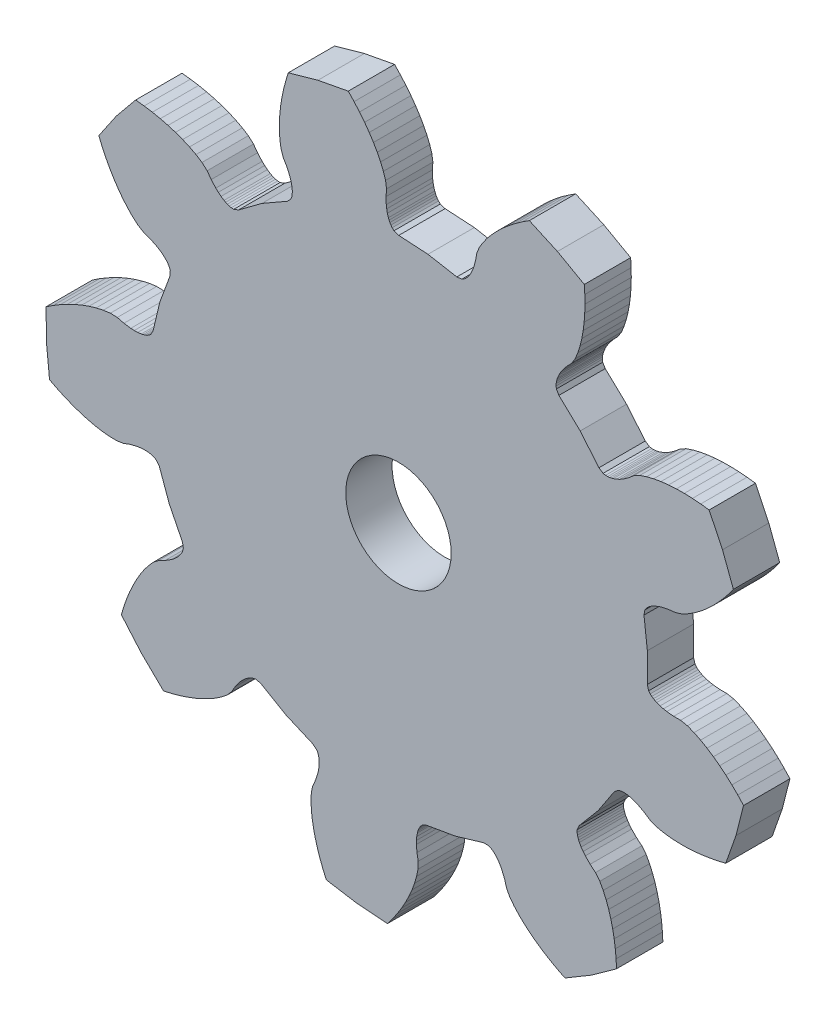
SolidWorks part; units mm, degrees
ref_plane "Front Plane" through (0, 0, 0) normal (0, 0, 1) x (1, 0, 0)
ref_plane "Top Plane" through (0, 0, 0) normal (0, 1, 0) x (1, 0, 0)
ref_plane "Right Plane" through (0, 0, 0) normal (1, 0, 0) x (0, 0, -1)
sketch "Sketch2" plane through (0, 0, 0) normal (0, 0, 1) x (1, 0, 0)
  line B0 (-34.2742, -4.342) -> (-34.5965, -3.9)
  line B1 (-34.5965, -3.9) -> (-34.8297, -3.7619)
  line B2 (-34.8297, -3.7619) -> (-35.0471, -3.6778)
  line B3 (-35.0471, -3.6778) -> (-35.2561, -3.6237)
  line B4 (-35.2561, -3.6237) -> (-35.4598, -3.5899)
  line B5 (-35.4598, -3.5899) -> (-35.6592, -3.5714)
  line B6 (-35.6592, -3.5714) -> (-36.0489, -3.5686)
  line B7 (-36.0489, -3.5686) -> (-36.4296, -3.6016)
  line B8 (-36.4296, -3.6016) -> (-36.8032, -3.6628)
  line B9 (-36.8032, -3.6628) -> (-37.534, -3.8523)
  line B10 (-37.534, -3.8523) -> (-38.2467, -4.1154)
  line B11 (-38.2467, -4.1154) -> (-38.9968, -4.2267)
  line B12 (-38.9968, -4.2267) -> (-39.7783, -4.2071)
  line B13 (-39.7783, -4.2071) -> (-40.5741, -4.1215)
  line B14 (-40.5741, -4.1215) -> (-41.3803, -3.9793)
  line B15 (-41.3803, -3.9793) -> (-42.1946, -3.7852)
  line B16 (-42.1946, -3.7852) -> (-43.0148, -3.5424)
  line B17 (-43.0148, -3.5424) -> (-43.839, -3.2531)
  line B18 (-43.839, -3.2531) -> (-44.6661, -2.9186)
  line B19 (-44.6661, -2.9186) -> (-45.4939, -2.5401)
  line B20 (-45.4939, -2.5401) -> (-46.3214, -2.1185)
  line B21 (-46.3214, -2.1185) -> (-46.6574, 1.2447)
  line B22 (-46.6574, 1.2447) -> (-46.6983, 4.6242)
  line B23 (-46.6983, 4.6242) -> (-45.9231, 5.1355)
  line B24 (-45.9231, 5.1355) -> (-45.1426, 5.6039)
  line B25 (-45.1426, 5.6039) -> (-44.358, 6.0286)
  line B26 (-44.358, 6.0286) -> (-43.5711, 6.4081)
  line B27 (-43.5711, 6.4081) -> (-42.7832, 6.7405)
  line B28 (-42.7832, 6.7405) -> (-41.9955, 7.0243)
  line B29 (-41.9955, 7.0243) -> (-41.2101, 7.2554)
  line B30 (-41.2101, 7.2554) -> (-40.4291, 7.4291)
  line B31 (-40.4291, 7.4291) -> (-39.6544, 7.5358)
  line B32 (-39.6544, 7.5358) -> (-38.8965, 7.5089)
  line B33 (-38.8965, 7.5089) -> (-38.1591, 7.3268)
  line B34 (-38.1591, 7.3268) -> (-37.4118, 7.2198)
  line B35 (-37.4118, 7.2198) -> (-37.0336, 7.2008)
  line B36 (-37.0336, 7.2008) -> (-36.6516, 7.2104)
  line B37 (-36.6516, 7.2104) -> (-36.2645, 7.2564)
  line B38 (-36.2645, 7.2564) -> (-36.0684, 7.2973)
  line B39 (-36.0684, 7.2973) -> (-35.87, 7.3534)
  line B40 (-35.87, 7.3534) -> (-35.6681, 7.4307)
  line B41 (-35.6681, 7.4307) -> (-35.4614, 7.5384)
  line B42 (-35.4614, 7.5384) -> (-35.2452, 7.7017)
  line B43 (-35.2452, 7.7017) -> (-34.9742, 8.1769)
  line B44 (-34.9742, 8.1769) -> (-34.2279, 11.3014)
  line B45 (-34.2279, 11.3014) -> (-33.1205, 14.3166)
  line B46 (-33.1205, 14.3166) -> (-33.0832, 14.8624)
  line B47 (-33.0832, 14.8624) -> (-33.1728, 15.118)
  line B48 (-33.1728, 15.118) -> (-33.2856, 15.3222)
  line B49 (-33.2856, 15.3222) -> (-33.4111, 15.498)
  line B50 (-33.4111, 15.498) -> (-33.5452, 15.6547)
  line B51 (-33.5452, 15.6547) -> (-33.6859, 15.7972)
  line B52 (-33.6859, 15.7972) -> (-33.9828, 16.0499)
  line B53 (-33.9828, 16.0499) -> (-34.2958, 16.2691)
  line B54 (-34.2958, 16.2691) -> (-34.6211, 16.4626)
  line B55 (-34.6211, 16.4626) -> (-35.3029, 16.7873)
  line B56 (-35.3029, 16.7873) -> (-36.0179, 17.0435)
  line B57 (-36.0179, 17.0435) -> (-36.664, 17.4405)
  line B58 (-36.664, 17.4405) -> (-37.2503, 17.9579)
  line B59 (-37.2503, 17.9579) -> (-37.8048, 18.535)
  line B60 (-37.8048, 18.535) -> (-38.3308, 19.1622)
  line B61 (-38.3308, 19.1622) -> (-38.8299, 19.8342)
  line B62 (-38.8299, 19.8342) -> (-39.3021, 20.5475)
  line B63 (-39.3021, 20.5475) -> (-39.7476, 21.2991)
  line B64 (-39.7476, 21.2991) -> (-40.1662, 22.0867)
  line B65 (-40.1662, 22.0867) -> (-40.5571, 22.9089)
  line B66 (-40.5571, 22.9089) -> (-40.9198, 23.7636)
  line B67 (-40.9198, 23.7636) -> (-39.0153, 26.5558)
  line B68 (-39.0153, 26.5558) -> (-36.8744, 29.171)
  line B69 (-36.8744, 29.171) -> (-35.9521, 29.0646)
  line B70 (-35.9521, 29.0646) -> (-35.0529, 28.9216)
  line B71 (-35.0529, 28.9216) -> (-34.1792, 28.7425)
  line B72 (-34.1792, 28.7425) -> (-33.3323, 28.5274)
  line B73 (-33.3323, 28.5274) -> (-32.515, 28.2757)
  line B74 (-32.515, 28.2757) -> (-31.7293, 27.9869)
  line B75 (-31.7293, 27.9869) -> (-30.979, 27.6592)
  line B76 (-30.979, 27.6592) -> (-30.2688, 27.2902)
  line B77 (-30.2688, 27.2902) -> (-29.6069, 26.8739)
  line B78 (-29.6069, 26.8739) -> (-29.0438, 26.3661)
  line B79 (-29.0438, 26.3661) -> (-28.596, 25.7524)
  line B80 (-28.596, 25.7524) -> (-28.0921, 25.1903)
  line B81 (-28.0921, 25.1903) -> (-27.8147, 24.9325)
  line B82 (-27.8147, 24.9325) -> (-27.5157, 24.6945)
  line B83 (-27.5157, 24.6945) -> (-27.1898, 24.4809)
  line B84 (-27.1898, 24.4809) -> (-27.0133, 24.3859)
  line B85 (-27.0133, 24.3859) -> (-26.8251, 24.3016)
  line B86 (-26.8251, 24.3016) -> (-26.6209, 24.231)
  line B87 (-26.6209, 24.231) -> (-26.3933, 24.1804)
  line B88 (-26.3933, 24.1804) -> (-26.1228, 24.1667)
  line B89 (-26.1228, 24.1667) -> (-25.6097, 24.3565)
  line B90 (-25.6097, 24.3565) -> (-23.0298, 26.2703)
  line B91 (-23.0298, 26.2703) -> (-20.2432, 27.8683)
  line B92 (-20.2432, 27.8683) -> (-19.8637, 28.2625)
  line B93 (-19.8637, 28.2625) -> (-19.7682, 28.516)
  line B94 (-19.7682, 28.516) -> (-19.7233, 28.7448)
  line B95 (-19.7233, 28.7448) -> (-19.7062, 28.96)
  line B96 (-19.7062, 28.96) -> (-19.7083, 29.1665)
  line B97 (-19.7083, 29.1665) -> (-19.7245, 29.3661)
  line B98 (-19.7245, 29.3661) -> (-19.7898, 29.7504)
  line B99 (-19.7898, 29.7504) -> (-19.8884, 30.1195)
  line B100 (-19.8884, 30.1195) -> (-20.0133, 30.4768)
  line B101 (-20.0133, 30.4768) -> (-20.3268, 31.1637)
  line B102 (-20.3268, 31.1637) -> (-20.7098, 31.8197)
  line B103 (-20.7098, 31.8197) -> (-20.9496, 32.5391)
  line B104 (-20.9496, 32.5391) -> (-21.0662, 33.3122)
  line B105 (-21.0662, 33.3122) -> (-21.12, 34.1108)
  line B106 (-21.12, 34.1108) -> (-21.1198, 34.9295)
  line B107 (-21.1198, 34.9295) -> (-21.0702, 35.7649)
  line B108 (-21.0702, 35.7649) -> (-20.9735, 36.6148)
  line B109 (-20.9735, 36.6148) -> (-20.8317, 37.4768)
  line B110 (-20.8317, 37.4768) -> (-20.6458, 38.3493)
  line B111 (-20.6458, 38.3493) -> (-20.4169, 39.2304)
  line B112 (-20.4169, 39.2304) -> (-20.1452, 40.1184)
  line B113 (-20.1452, 40.1184) -> (-16.8917, 41.0333)
  line B114 (-16.8917, 41.0333) -> (-13.5706, 41.6605)
  line B115 (-13.5706, 41.6605) -> (-12.9323, 40.9858)
  line B116 (-12.9323, 40.9858) -> (-12.3354, 40.2985)
  line B117 (-12.3354, 40.2985) -> (-11.7812, 39.5998)
  line B118 (-11.7812, 39.5998) -> (-11.2709, 38.8906)
  line B119 (-11.2709, 38.8906) -> (-10.8063, 38.1723)
  line B120 (-10.8063, 38.1723) -> (-10.3903, 37.4461)
  line B121 (-10.3903, 37.4461) -> (-10.0263, 36.7128)
  line B122 (-10.0263, 36.7128) -> (-9.7195, 35.9737)
  line B123 (-9.7195, 35.9737) -> (-9.48, 35.2292)
  line B124 (-9.48, 35.2292) -> (-9.3748, 34.4781)
  line B125 (-9.3748, 34.4781) -> (-9.4261, 33.7204)
  line B126 (-9.4261, 33.7204) -> (-9.4017, 32.9658)
  line B127 (-9.4017, 32.9658) -> (-9.3547, 32.5901)
  line B128 (-9.3547, 32.5901) -> (-9.279, 32.2155)
  line B129 (-9.279, 32.2155) -> (-9.1665, 31.8423)
  line B130 (-9.1665, 31.8423) -> (-9.0923, 31.6564)
  line B131 (-9.0923, 31.6564) -> (-9.0024, 31.4705)
  line B132 (-9.0024, 31.4705) -> (-8.8914, 31.2853)
  line B133 (-8.8914, 31.2853) -> (-8.7494, 31.1004)
  line B134 (-8.7494, 31.1004) -> (-8.5511, 30.9158)
  line B135 (-8.5511, 30.9158) -> (-8.036, 30.7313)
  line B136 (-8.036, 30.7313) -> (-4.8295, 30.5391)
  line B137 (-4.8295, 30.5391) -> (-1.6677, 29.9719)
  line B138 (-1.6677, 29.9719) -> (-1.1236, 30.0301)
  line B139 (-1.1236, 30.0301) -> (-0.8874, 30.1629)
  line B140 (-0.8874, 30.1629) -> (-0.706, 30.3092)
  line B141 (-0.706, 30.3092) -> (-0.5546, 30.4634)
  line B142 (-0.5546, 30.4634) -> (-0.4236, 30.6226)
  line B143 (-0.4236, 30.6226) -> (-0.3078, 30.786)
  line B144 (-0.3078, 30.786) -> (-0.1107, 31.1223)
  line B145 (-0.1107, 31.1223) -> (0.0511, 31.4685)
  line B146 (0.0511, 31.4685) -> (0.1853, 31.8225)
  line B147 (0.1853, 31.8225) -> (0.3864, 32.5502)
  line B148 (0.3864, 32.5502) -> (0.5147, 33.299)
  line B149 (0.5147, 33.299) -> (0.7936, 34.0041)
  line B150 (0.7936, 34.0041) -> (1.2013, 34.6714)
  line B151 (1.2013, 34.6714) -> (1.6732, 35.3176)
  line B152 (1.6732, 35.3176) -> (2.1995, 35.9447)
  line B153 (2.1995, 35.9447) -> (2.7748, 36.5528)
  line B154 (2.7748, 36.5528) -> (3.3951, 37.1418)
  line B155 (3.3951, 37.1418) -> (4.0577, 37.711)
  line B156 (4.0577, 37.711) -> (4.7611, 38.2599)
  line B157 (4.7611, 38.2599) -> (5.5027, 38.7877)
  line B158 (5.5027, 38.7877) -> (6.2815, 39.2932)
  line B159 (6.2815, 39.2932) -> (9.362, 37.9028)
  line B160 (9.362, 37.9028) -> (12.3094, 36.2485)
  line B161 (12.3094, 36.2485) -> (12.3646, 35.3214)
  line B162 (12.3646, 35.3214) -> (12.38, 34.4113)
  line B163 (12.38, 34.4113) -> (12.3554, 33.5195)
  line B164 (12.3554, 33.5195) -> (12.2906, 32.6483)
  line B165 (12.2906, 32.6483) -> (12.1847, 31.7997)
  line B166 (12.1847, 31.7997) -> (12.0364, 30.9757)
  line B167 (12.0364, 30.9757) -> (11.8441, 30.1799)
  line B168 (11.8441, 30.1799) -> (11.6038, 29.4166)
  line B169 (11.6038, 29.4166) -> (11.3089, 28.6925)
  line B170 (11.3089, 28.6925) -> (10.9066, 28.0496)
  line B171 (10.9066, 28.0496) -> (10.3803, 27.502)
  line B172 (10.3803, 27.502) -> (9.914, 26.9084)
  line B173 (9.914, 26.9084) -> (9.7085, 26.5904)
  line B174 (9.7085, 26.5904) -> (9.5259, 26.2546)
  line B175 (9.5259, 26.2546) -> (9.3722, 25.8965)
  line B176 (9.3722, 25.8965) -> (9.3094, 25.7062)
  line B177 (9.3094, 25.7062) -> (9.2589, 25.5061)
  line B178 (9.2589, 25.5061) -> (9.2246, 25.293)
  line B179 (9.2246, 25.293) -> (9.2147, 25.06)
  line B180 (9.2147, 25.06) -> (9.248, 24.7911)
  line B181 (9.248, 24.7911) -> (9.5238, 24.3186)
  line B182 (9.5238, 24.3186) -> (11.8568, 22.1103)
  line B183 (11.8568, 22.1103) -> (13.9142, 19.6435)
  line B184 (13.9142, 19.6435) -> (14.3684, 19.3384)
  line B185 (14.3684, 19.3384) -> (14.6346, 19.2881)
  line B186 (14.6346, 19.2881) -> (14.8677, 19.2838)
  line B187 (14.8677, 19.2838) -> (15.0826, 19.3044)
  line B188 (15.0826, 19.3044) -> (15.2856, 19.3422)
  line B189 (15.2856, 19.3422) -> (15.4794, 19.393)
  line B190 (15.4794, 19.393) -> (15.8464, 19.5239)
  line B191 (15.8464, 19.5239) -> (16.1928, 19.6851)
  line B192 (16.1928, 19.6851) -> (16.5233, 19.8703)
  line B193 (16.5233, 19.8703) -> (17.1451, 20.2983)
  line B194 (17.1451, 20.2983) -> (17.7245, 20.7893)
  line B195 (17.7245, 20.7893) -> (18.3915, 21.1502)
  line B196 (18.3915, 21.1502) -> (19.1326, 21.3994)
  line B197 (19.1326, 21.3994) -> (19.9096, 21.5909)
  line B198 (19.9096, 21.5909) -> (20.7158, 21.7331)
  line B199 (20.7158, 21.7331) -> (21.5474, 21.8292)
  line B200 (21.5474, 21.8292) -> (22.4011, 21.8817)
  line B201 (22.4011, 21.8817) -> (23.2749, 21.8916)
  line B202 (23.2749, 21.8916) -> (24.1662, 21.8601)
  line B203 (24.1662, 21.8601) -> (25.0737, 21.7878)
  line B204 (25.0737, 21.7878) -> (25.9955, 21.6745)
  line B205 (25.9955, 21.6745) -> (27.4613, 18.629)
  line B206 (27.4613, 18.629) -> (28.6556, 15.4672)
  line B207 (28.6556, 15.4672) -> (28.1021, 14.7217)
  line B208 (28.1021, 14.7217) -> (27.5289, 14.0146)
  line B209 (27.5289, 14.0146) -> (26.9368, 13.3473)
  line B210 (26.9368, 13.3473) -> (26.3272, 12.7215)
  line B211 (26.3272, 12.7215) -> (25.7003, 12.1396)
  line B212 (25.7003, 12.1396) -> (25.0574, 11.6036)
  line B213 (25.0574, 11.6036) -> (24.3986, 11.1177)
  line B214 (24.3986, 11.1177) -> (23.7239, 10.6872)
  line B215 (23.7239, 10.6872) -> (23.0323, 10.3222)
  line B216 (23.0323, 10.3222) -> (22.3109, 10.0883)
  line B217 (22.3109, 10.0883) -> (21.5558, 10.0072)
  line B218 (21.5558, 10.0072) -> (20.8169, 9.852)
  line B219 (20.8169, 9.852) -> (20.4552, 9.7405)
  line B220 (20.4552, 9.7405) -> (20.0994, 9.6008)
  line B221 (20.0994, 9.6008) -> (19.7514, 9.4253)
  line B222 (19.7514, 9.4253) -> (19.5812, 9.3199)
  line B223 (19.5812, 9.3199) -> (19.4138, 9.199)
  line B224 (19.4138, 9.199) -> (19.2505, 9.0575)
  line B225 (19.2505, 9.0575) -> (19.093, 8.8858)
  line B226 (19.093, 8.8858) -> (18.9459, 8.6582)
  line B227 (18.9459, 8.6582) -> (18.8535, 8.119)
  line B228 (18.8535, 8.119) -> (19.221, 4.9277)
  line B229 (19.221, 4.9277) -> (19.2116, 1.7157)
  line B230 (19.2116, 1.7157) -> (19.3633, 1.1901)
  line B231 (19.3633, 1.1901) -> (19.5352, 0.9803)
  line B232 (19.5352, 0.9803) -> (19.7107, 0.8272)
  line B233 (19.7107, 0.8272) -> (19.8888, 0.7047)
  line B234 (19.8888, 0.7047) -> (20.0684, 0.6034)
  line B235 (20.0684, 0.6034) -> (20.2495, 0.5175)
  line B236 (20.2495, 0.5175) -> (20.615, 0.3819)
  line B237 (20.615, 0.3819) -> (20.9838, 0.2826)
  line B238 (20.9838, 0.2826) -> (21.3559, 0.2122)
  line B239 (21.3559, 0.2122) -> (22.1075, 0.1404)
  line B240 (22.1075, 0.1404) -> (22.8669, 0.1442)
  line B241 (22.8669, 0.1442) -> (23.6099, -0.008)
  line B242 (23.6099, -0.008) -> (24.3379, -0.2937)
  line B243 (24.3379, -0.2937) -> (25.0562, -0.6463)
  line B244 (25.0562, -0.6463) -> (25.7651, -1.0557)
  line B245 (25.7651, -1.0557) -> (26.4638, -1.5165)
  line B246 (26.4638, -1.5165) -> (27.1517, -2.0253)
  line B247 (27.1517, -2.0253) -> (27.8273, -2.579)
  line B248 (27.8273, -2.579) -> (28.49, -3.1761)
  line B249 (28.49, -3.1761) -> (29.1385, -3.8149)
  line B250 (29.1385, -3.8149) -> (29.7717, -4.4944)
  line B251 (29.7717, -4.4944) -> (28.9373, -7.7695)
  line B252 (28.9373, -7.7695) -> (27.8199, -10.9592)
  line B253 (27.8199, -10.9592) -> (26.9165, -11.1746)
  line B254 (26.9165, -11.1746) -> (26.0229, -11.3478)
  line B255 (26.0229, -11.3478) -> (25.1405, -11.4784)
  line B256 (25.1405, -11.4784) -> (24.2711, -11.5657)
  line B257 (24.2711, -11.5657) -> (23.4169, -11.6089)
  line B258 (23.4169, -11.6089) -> (22.5799, -11.6061)
  line B259 (22.5799, -11.6061) -> (21.7628, -11.5548)
  line B260 (21.7628, -11.5548) -> (20.9693, -11.4507)
  line B261 (20.9693, -11.4507) -> (20.205, -11.2861)
  line B262 (20.205, -11.2861) -> (19.502, -11.0016)
  line B263 (19.502, -11.0016) -> (18.8713, -10.5782)
  line B264 (18.8713, -10.5782) -> (18.2055, -10.2221)
  line B265 (18.2055, -10.2221) -> (17.8568, -10.075)
  line B266 (17.8568, -10.075) -> (17.4946, -9.9534)
  line B267 (17.4946, -9.9534) -> (17.1151, -9.8642)
  line B268 (17.1151, -9.8642) -> (16.9167, -9.8352)
  line B269 (16.9167, -9.8352) -> (16.711, -9.8205)
  line B270 (16.711, -9.8205) -> (16.4951, -9.8238)
  line B271 (16.4951, -9.8238) -> (16.264, -9.8543)
  line B272 (16.264, -9.8543) -> (16.0049, -9.9338)
  line B273 (16.0049, -9.9338) -> (15.5876, -10.2876)
  line B274 (15.5876, -10.2876) -> (13.8179, -12.9683)
  line B275 (13.8179, -12.9683) -> (11.7458, -15.423)
  line B276 (11.7458, -15.423) -> (11.5243, -15.9234)
  line B277 (11.5243, -15.9234) -> (11.521, -16.1941)
  line B278 (11.521, -16.1941) -> (11.5571, -16.4245)
  line B279 (11.5571, -16.4245) -> (11.6147, -16.6328)
  line B280 (11.6147, -16.6328) -> (11.6871, -16.8258)
  line B281 (11.6871, -16.8258) -> (11.771, -17.008)
  line B282 (11.771, -17.008) -> (11.9635, -17.3468)
  line B283 (11.9635, -17.3468) -> (12.1824, -17.66)
  line B284 (12.1824, -17.66) -> (12.4222, -17.9531)
  line B285 (12.4222, -17.9531) -> (12.9515, -18.4911)
  line B286 (12.9515, -18.4911) -> (13.5357, -18.9767)
  line B287 (13.5357, -18.9767) -> (14.0072, -19.5706)
  line B288 (14.0072, -19.5706) -> (14.3811, -20.2574)
  line B289 (14.3811, -20.2574) -> (14.7049, -20.9891)
  line B290 (14.7049, -20.9891) -> (14.9848, -21.7585)
  line B291 (14.9848, -21.7585) -> (15.2238, -22.5606)
  line B292 (15.2238, -22.5606) -> (15.4237, -23.3925)
  line B293 (15.4237, -23.3925) -> (15.5853, -24.251)
  line B294 (15.5853, -24.251) -> (15.709, -25.1344)
  line B295 (15.709, -25.1344) -> (15.7951, -26.0407)
  line B296 (15.7951, -26.0407) -> (15.8436, -26.9681)
  line B297 (15.8436, -26.9681) -> (13.0991, -28.9406)
  line B298 (13.0991, -28.9406) -> (10.1929, -30.6658)
  line B299 (10.1929, -30.6658) -> (9.3625, -30.25)
  line B300 (9.3625, -30.25) -> (8.5665, -29.8083)
  line B301 (8.5665, -29.8083) -> (7.8065, -29.3412)
  line B302 (7.8065, -29.3412) -> (7.0847, -28.8494)
  line B303 (7.0847, -28.8494) -> (6.4024, -28.3333)
  line B304 (6.4024, -28.3333) -> (5.7631, -27.793)
  line B305 (5.7631, -27.793) -> (5.1703, -27.2287)
  line B306 (5.1703, -27.2287) -> (4.629, -26.6389)
  line B307 (4.629, -26.6389) -> (4.1494, -26.0214)
  line B308 (4.1494, -26.0214) -> (3.7938, -25.3516)
  line B309 (3.7938, -25.3516) -> (3.5828, -24.6219)
  line B310 (3.5828, -24.6219) -> (3.3018, -23.9213)
  line B311 (3.3018, -23.9213) -> (3.1291, -23.5843)
  line B312 (3.1291, -23.5843) -> (2.9297, -23.2581)
  line B313 (2.9297, -23.2581) -> (2.6963, -22.946)
  line B314 (2.6963, -22.946) -> (2.5632, -22.7966)
  line B315 (2.5632, -22.7966) -> (2.4151, -22.6528)
  line B316 (2.4151, -22.6528) -> (2.2475, -22.5167)
  line B317 (2.2475, -22.5167) -> (2.0509, -22.3915)
  line B318 (2.0509, -22.3915) -> (1.8012, -22.2858)
  line B319 (1.8012, -22.2858) -> (1.2541, -22.2886)
  line B320 (1.2541, -22.2886) -> (-1.8246, -23.2048)
  line B321 (-1.8246, -23.2048) -> (-4.9897, -23.7532)
  line B322 (-4.9897, -23.7532) -> (-5.481, -23.994)
  line B323 (-5.481, -23.994) -> (-5.6578, -24.1995)
  line B324 (-5.6578, -24.1995) -> (-5.7782, -24.3991)
  line B325 (-5.7782, -24.3991) -> (-5.8678, -24.5954)
  line B326 (-5.8678, -24.5954) -> (-5.9364, -24.79)
  line B327 (-5.9364, -24.79) -> (-5.9895, -24.9833)
  line B328 (-5.9895, -24.9833) -> (-6.0596, -25.3666)
  line B329 (-6.0596, -25.3666) -> (-6.0931, -25.7473)
  line B330 (-6.0931, -25.7473) -> (-6.0979, -26.126)
  line B331 (-6.0979, -26.126) -> (-6.0383, -26.8784)
  line B332 (-6.0383, -26.8784) -> (-5.9029, -27.6259)
  line B333 (-5.9029, -27.6259) -> (-5.9234, -28.3838)
  line B334 (-5.9234, -28.3838) -> (-6.0784, -29.1504)
  line B335 (-6.0784, -29.1504) -> (-6.3009, -29.919)
  line B336 (-6.3009, -29.919) -> (-6.5811, -30.6884)
  line B337 (-6.5811, -30.6884) -> (-6.9135, -31.4565)
  line B338 (-6.9135, -31.4565) -> (-7.295, -32.222)
  line B339 (-7.295, -32.222) -> (-7.723, -32.9838)
  line B340 (-7.723, -32.9838) -> (-8.1962, -33.7399)
  line B341 (-8.1962, -33.7399) -> (-8.7126, -34.4895)
  line B342 (-8.7126, -34.4895) -> (-9.2717, -35.2312)
  line B343 (-9.2717, -35.2312) -> (-12.642, -34.9782)
  line B344 (-12.642, -34.9782) -> (-15.9773, -34.4316)
  line B345 (-15.9773, -34.4316) -> (-16.3461, -33.5794)
  line B346 (-16.3461, -33.5794) -> (-16.672, -32.7293)
  line B347 (-16.672, -32.7293) -> (-16.9539, -31.883)
  line B348 (-16.9539, -31.883) -> (-17.1909, -31.0422)
  line B349 (-17.1909, -31.0422) -> (-17.3816, -30.2083)
  line B350 (-17.3816, -30.2083) -> (-17.5241, -29.3836)
  line B351 (-17.5241, -29.3836) -> (-17.6156, -28.57)
  line B352 (-17.6156, -28.57) -> (-17.6509, -27.7704)
  line B353 (-17.6509, -27.7704) -> (-17.6214, -26.9891)
  line B354 (-17.6214, -26.9891) -> (-17.4634, -26.2475)
  line B355 (-17.4634, -26.2475) -> (-17.1558, -25.5528)
  line B356 (-17.1558, -25.5528) -> (-16.9209, -24.8355)
  line B357 (-16.9209, -24.8355) -> (-16.8366, -24.4662)
  line B358 (-16.8366, -24.4662) -> (-16.7797, -24.0885)
  line B359 (-16.7797, -24.0885) -> (-16.7578, -23.6993)
  line B360 (-16.7578, -23.6993) -> (-16.7639, -23.4989)
  line B361 (-16.7639, -23.4989) -> (-16.7847, -23.2937)
  line B362 (-16.7847, -23.2937) -> (-16.8256, -23.0816)
  line B363 (-16.8256, -23.0816) -> (-16.8957, -22.8593)
  line B364 (-16.8957, -22.8593) -> (-17.0192, -22.618)
  line B365 (-17.0192, -22.618) -> (-17.4401, -22.2685)
  line B366 (-17.4401, -22.2685) -> (-20.3875, -20.9912)
  line B367 (-20.3875, -20.9912) -> (-23.1645, -19.3768)
  line B368 (-23.1645, -19.3768) -> (-23.6956, -19.2454)
  line B369 (-23.6956, -19.2454) -> (-23.963, -19.2894)
  line B370 (-23.963, -19.2894) -> (-24.1835, -19.3648)
  line B371 (-24.1835, -19.3648) -> (-24.3786, -19.4578)
  line B372 (-24.3786, -19.4578) -> (-24.5561, -19.5627)
  line B373 (-24.5561, -19.5627) -> (-24.721, -19.6767)
  line B374 (-24.721, -19.6767) -> (-25.0212, -19.9254)
  line B375 (-25.0212, -19.9254) -> (-25.2917, -20.1951)
  line B376 (-25.2917, -20.1951) -> (-25.5386, -20.4822)
  line B377 (-25.5386, -20.4822) -> (-25.9765, -21.0971)
  line B378 (-25.9765, -21.0971) -> (-26.3532, -21.7567)
  line B379 (-26.3532, -21.7567) -> (-26.8563, -22.3242)
  line B380 (-26.8563, -22.3242) -> (-27.4677, -22.8116)
  line B381 (-27.4677, -22.8116) -> (-28.1324, -23.2576)
  line B382 (-28.1324, -23.2576) -> (-28.8414, -23.6668)
  line B383 (-28.8414, -23.6668) -> (-29.5899, -24.0415)
  line B384 (-29.5899, -24.0415) -> (-30.3742, -24.3828)
  line B385 (-30.3742, -24.3828) -> (-31.1916, -24.6909)
  line B386 (-31.1916, -24.6909) -> (-32.0402, -24.9663)
  line B387 (-32.0402, -24.9663) -> (-32.9175, -25.2083)
  line B388 (-32.9175, -25.2083) -> (-33.8226, -25.4171)
  line B389 (-33.8226, -25.4171) -> (-36.2416, -23.057)
  line B390 (-36.2416, -23.057) -> (-38.4454, -20.4944)
  line B391 (-38.4454, -20.4944) -> (-38.1802, -19.6046)
  line B392 (-38.1802, -19.6046) -> (-37.8832, -18.7438)
  line B393 (-37.8832, -18.7438) -> (-37.5553, -17.9145)
  line B394 (-37.5553, -17.9145) -> (-37.1964, -17.1179)
  line B395 (-37.1964, -17.1179) -> (-36.8065, -16.3564)
  line B396 (-36.8065, -16.3564) -> (-36.3854, -15.633)
  line B397 (-36.3854, -15.633) -> (-35.9325, -14.9511)
  line B398 (-35.9325, -14.9511) -> (-35.4459, -14.3158)
  line B399 (-35.4459, -14.3158) -> (-34.9208, -13.7364)
  line B400 (-34.9208, -13.7364) -> (-34.3232, -13.2698)
  line B401 (-34.3232, -13.2698) -> (-33.6412, -12.9353)
  line B402 (-33.6412, -12.9353) -> (-32.9998, -12.5368)
  line B403 (-32.9998, -12.5368) -> (-32.6981, -12.3082)
  line B404 (-32.6981, -12.3082) -> (-32.4116, -12.0555)
  line B405 (-32.4116, -12.0555) -> (-32.1446, -11.7712)
  line B406 (-32.1446, -11.7712) -> (-32.0207, -11.614)
  line B407 (-32.0207, -11.614) -> (-31.9046, -11.4433)
  line B408 (-31.9046, -11.4433) -> (-31.7997, -11.2546)
  line B409 (-31.7997, -11.2546) -> (-31.7105, -11.0392)
  line B410 (-31.7105, -11.0392) -> (-31.6498, -10.775)
  line B411 (-31.6498, -10.775) -> (-31.7476, -10.2368)
  line B412 (-31.7476, -10.2368) -> (-33.1845, -7.3638)
  line B413 (-33.1845, -7.3638) -> (-34.2742, -4.342)
  circle B414 centre (-8.0654, 3.4022) radius 5.7785
sketch_block_instance "dgfhfdhdfhdfhdfh-1"
sketch_block "dgfhfdhdfhdfhdfh"
extrude "Boss-Extrude2" add sketch "Sketch2" along normal blind 5.08
